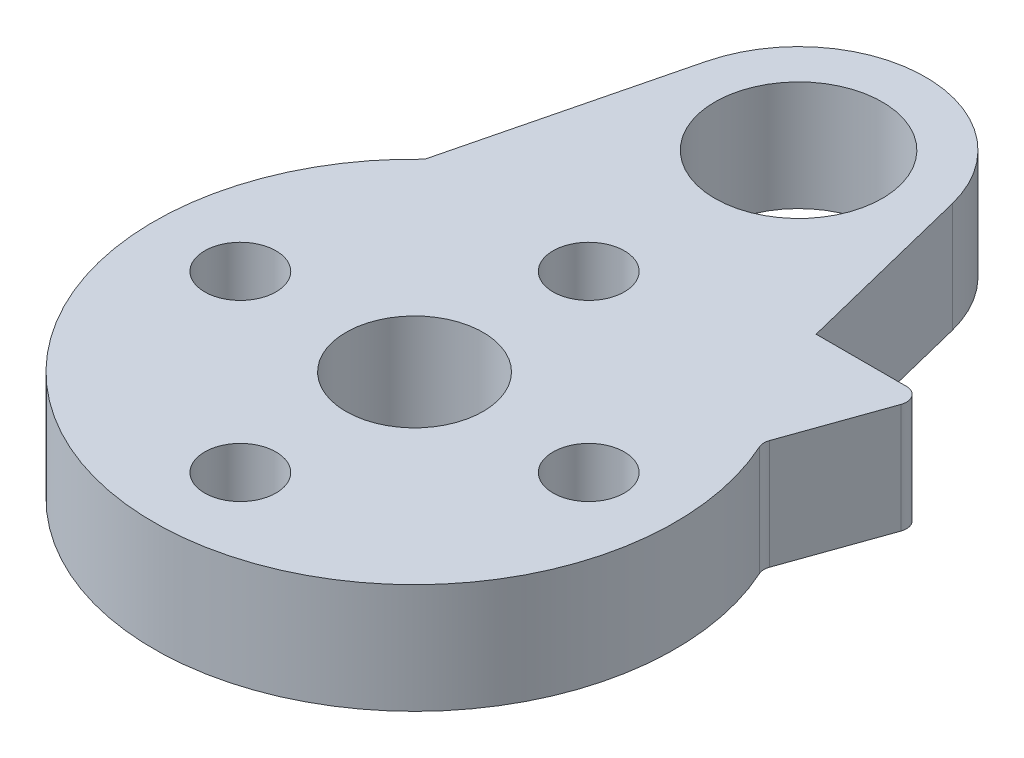
SolidWorks part; units mm, degrees
material "Tough 2000"
ref_plane "Front Plane" through (0, 0, 0) normal (0, 0, 1) x (1, 0, 0)
ref_plane "Top Plane" through (0, 0, 0) normal (0, 1, 0) x (1, 0, 0)
ref_plane "Right Plane" through (0, 0, 0) normal (1, 0, 0) x (0, 0, -1)
sketch "Sketch1" plane through (0, 0, 0) normal (0, 1, 0) x (1, 0, 0)
  line L1 (-4.4887, 15.1149) -> (-7.7641, 1.9285)
  line L2 (4.4887, 15.1149) -> (7.7641, 1.9285)
  arc A0 (-7.7641, 1.9285) -> (7.7641, 1.9285) centre (0, 0) ccw
  arc A1 (4.4887, 15.1149) -> (-4.4887, 15.1149) centre (0, 14) ccw
  circle A2 centre (0, 14) radius 3.05
  circle A3 centre (0, 0) radius 2.5
  dimension "D1" = 14
  dimension "D2" = 4.6251
  dimension "D3" = 8
extrude "Boss-Extrude1" add sketch "Sketch1" along normal blind 4
sketch "Sketch2" plane through (0, 4, 0) normal (0, 1, 0) x (1, 0, 0)
  line L0 (0, 0) -> (0, 6.35) construction
  circle A0 centre (0, 6.35) radius 1.3
  circle A1 centre (6.35, 0) radius 1.3
  circle A2 centre (0, -6.35) radius 1.3
  circle A3 centre (-6.35, 0) radius 1.3
  point P13 (0, 0)
  dimension "D1" = 4
extrude "Cut-Extrude1" cut sketch "Sketch2" against normal blind 4
sketch "Sketch3" plane through (0, 4, 0) normal (0, 1, 0) x (1, 0, 0)
  circle A4 centre (0, 0) radius 7.65
  arc A5 (-1.5493, 9.3728) -> (1.5493, 9.3728) centre (0, 0) ccw
  arc A6 (-1.5493, 9.3728) -> (1.5493, 9.3728) centre (0, 14) ccw
extrude "Boss-Extrude2" add sketch "Sketch3" against normal blind 4
sketch "Sketch4" plane through (0, 4, 0) normal (0, 1, 0) x (1, 0, 0)
  line L8 (6.529, 6.9009) -> (4.4887, 15.1149) construction
  line L14 (2.1651, 1.25) -> (5.0731, 2.929)
  line L19 (1.7931, 1.7421) -> (6.1292, 8.5104)
  line L20 (6.1292, 8.5104) -> (10.1292, 8.5104)
  line L22 (5.0731, 2.929) -> (5.5955, 4.1053)
  line L23 (5.5955, 4.1053) -> (8.5672, 4.1053)
  line L24 (8.5672, 4.1053) -> (10.1292, 8.5104)
  arc A3 (2.1651, 1.25) -> (1.7931, 1.7421) centre (0, 0) ccw
  arc A5 (-6.529, 6.9009) -> (6.529, 6.9009) centre (0, 0) ccw construction
extrude "Boss-Extrude3" add sketch "Sketch4" against normal up to surface (4 mm away) up to face at (0, 0, -7.7852)
fillet "Fillet9" radius 0.5 2 edges at (8.5672, 2, -4.1053) (10.1292, 2, -8.5104)
